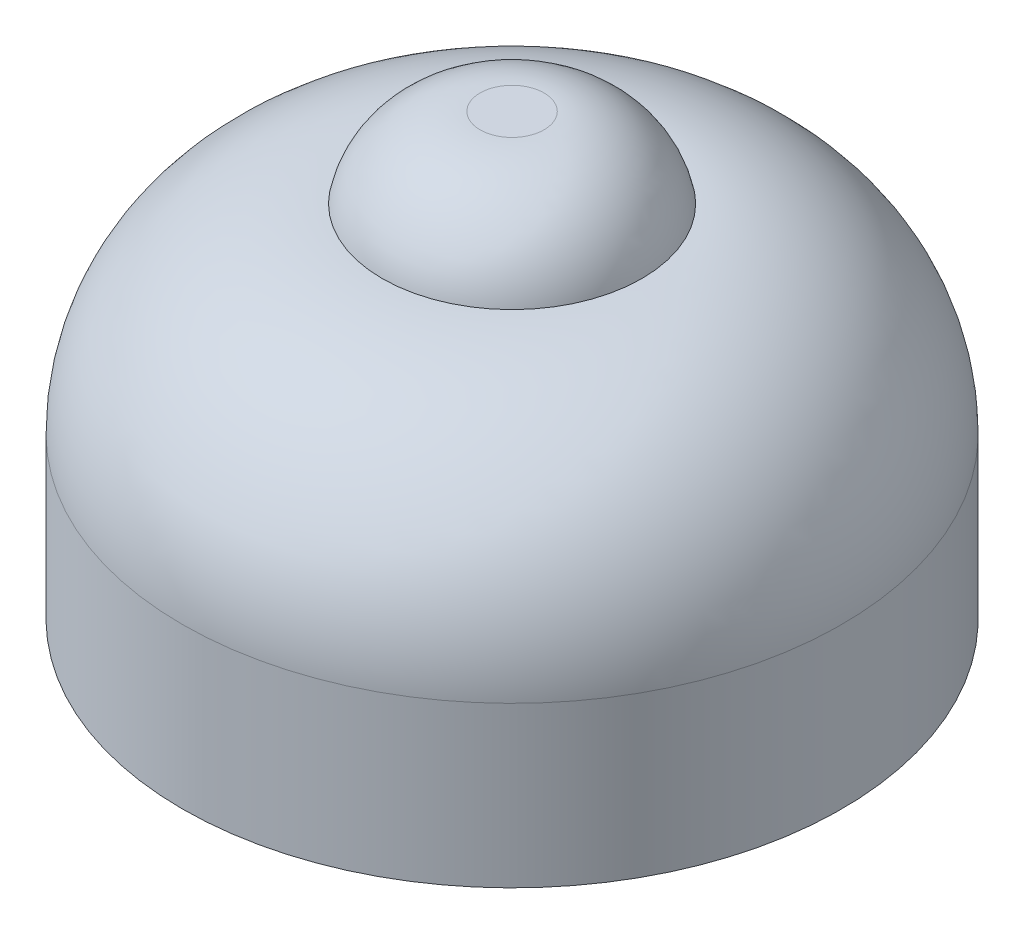
SolidWorks part; units mm, degrees
ref_plane "Front Plane" through (0, 0, 0) normal (0, 0, 1) x (1, 0, 0)
ref_plane "Top Plane" through (0, 0, 0) normal (0, 1, 0) x (1, 0, 0)
ref_plane "Right Plane" through (0, 0, 0) normal (1, 0, 0) x (0, 0, -1)
sketch "Sketch1" plane through (0, 0, 0) normal (0, 1, 0) x (1, 0, 0)
  circle A0 centre (0, 0) radius 16.5
  dimension "D1" = 33
extrude "Boss-Extrude1" add sketch "Sketch1" along normal blind 18
fillet "Fillet1" radius 10 1 edges at (0, 18, 16.5)
sketch "Sketch2" plane through (0, 18, 0) normal (0, 1, 0) x (1, 0, 0)
  circle A0 centre (0, 0) radius 6.5
extrude "Boss-Extrude2" add sketch "Sketch2" along normal blind 4
fillet "Fillet5" radius 5 1 edges at (0, 22, 6.5)
